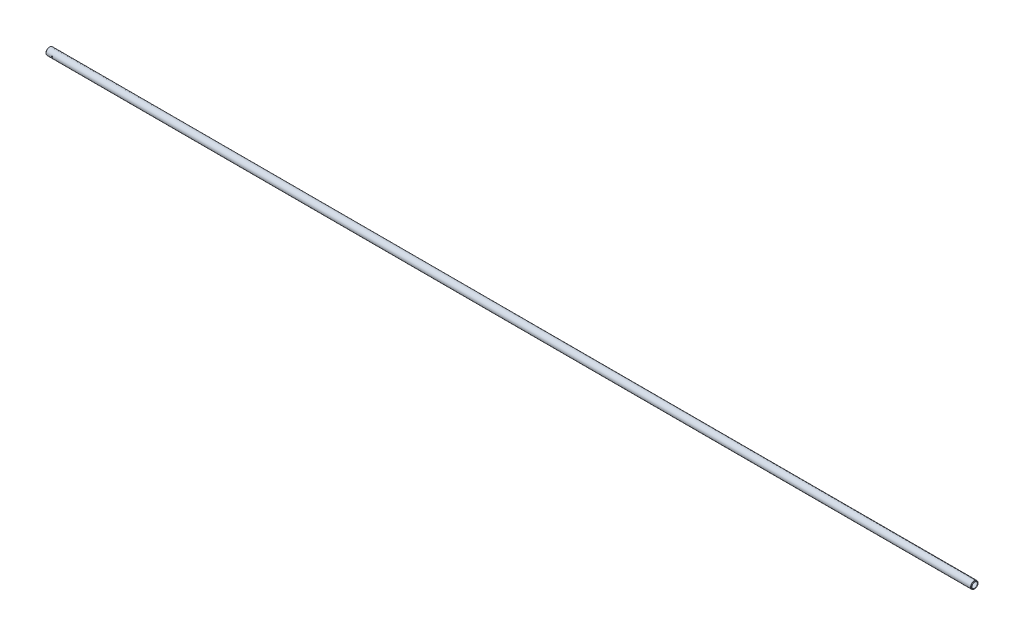
SolidWorks part; units mm, degrees
ref_plane "Front Plane" through (0, 0, 0) normal (0, 0, 1) x (1, 0, 0)
ref_plane "Top Plane" through (0, 0, 0) normal (0, 1, 0) x (1, 0, 0)
ref_plane "Right Plane" through (0, 0, 0) normal (1, 0, 0) x (0, 0, -1)
ref_plane "Plane1" through (1156.6271, 0, 0) normal (1, 0, 0) x (0, 0, -1)
sketch "Sketch1" plane through (0, 0, 0) normal (0, 0, 1) x (1, 0, 0)
  line L0 (-0.445, 3.6899) -> (-0.2794, 3.5242)
  line L1 (-0.2794, 3.5242) -> (0, 3.5242)
  line L2 (0, 3.5242) -> (0.5588, 4.0831)
  line L3 (0.5588, 4.0831) -> (1156.0683, 4.0831)
  line L4 (1156.0683, 4.0831) -> (1156.6271, 3.5242)
  line L5 (1156.6271, 3.5242) -> (1156.9065, 3.5242)
  line L6 (1156.9065, 3.5242) -> (1157.0721, 3.6899)
  line L7 (1157.0721, 3.8695) -> (1156.546, 4.3956)
  line L8 (1156.1509, 4.5593) -> (0.4762, 4.5593)
  line L9 (0.0811, 4.3956) -> (-0.445, 3.8695)
  line L10 (1156.6271, 0) -> (0, 0) construction
  arc A0 (-0.445, 3.8695) -> (-0.445, 3.6899) centre (-0.3552, 3.7797) ccw
  arc A1 (1157.0721, 3.6899) -> (1157.0721, 3.8695) centre (1156.9823, 3.7797) ccw
  arc A2 (1156.546, 4.3956) -> (1156.1509, 4.5593) centre (1156.1509, 4.0005) ccw
  arc A3 (0.4762, 4.5593) -> (0.0811, 4.3956) centre (0.4763, 4.0005) ccw
revolve "Revolve1" add sketch "Sketch1" angle 360 about L10 reverse direction yes
sketch "Sketch2" plane through (0, 0, 0) normal (0, 0, 1) x (1, 0, 0)
  circle A0 centre (7.6962, 0) radius 0.7874
extrude "Cut-Extrude1" cut sketch "Sketch2" along normal blind 4.5593
ref_plane "Plane2" through (578.3135, 0, 0) normal (1, 0, 0) x (0, 0, -1)
ref_plane "cp1 XY" through (578.3135, 0, 0) normal (1, 0, 0) x (0, 0, -1)
ref_plane "cp1 XZ" through (0, 4.5593, 0) normal (0, -1, 0) x (-1, 0, 0)
ref_plane "cp1 YZ" through (0, 0, 0) normal (0, 0, -1) x (-1, 0, 0)
ref_axis "cp1 X" through (578.3135, 4.5593, 80.9) along (0, 0, -1)
ref_axis "cp1 Y" through (578.3135, -50, 0) along (0, 1, 0)
ref_axis "cp1 Z" through (80.9, 4.5593, 0) along (-1, 0, 0)
sketch3d "cp1"
  point P0 (578.3135, 4.5593, 0)
ref_plane "cp2 XY" through (578.3135, 0, 0) normal (1, 0, 0) x (0, 0, -1)
ref_plane "cp2 XZ" through (0, 0, 0) normal (0, -1, 0) x (-1, 0, 0)
ref_plane "cp2 YZ" through (0, 0, -4.5593) normal (0, 0, -1) x (-1, 0, 0)
ref_axis "cp2 X" through (578.3135, 0, 80.9) along (0, 0, -1)
ref_axis "cp2 Y" through (578.3135, -50, -4.5593) along (0, 1, 0)
ref_axis "cp2 Z" through (80.9, 0, -4.5593) along (-1, 0, 0)
sketch3d "cp2"
  point P0 (578.3135, 0, -4.5593)
ref_plane "cp3 XY" through (578.3135, 0, 0) normal (1, 0, 0) x (0, 0, -1)
ref_plane "cp3 XZ" through (0, -4.5593, 0) normal (0, -1, 0) x (-1, 0, 0)
ref_plane "cp3 YZ" through (0, 0, 0) normal (0, 0, -1) x (-1, 0, 0)
ref_axis "cp3 X" through (578.3135, -4.5593, 80.9) along (0, 0, -1)
ref_axis "cp3 Y" through (578.3135, -50, 0) along (0, 1, 0)
ref_axis "cp3 Z" through (80.9, -4.5593, 0) along (-1, 0, 0)
sketch3d "cp3"
  point P0 (578.3135, -4.5593, 0)
ref_plane "cp4 XY" through (578.3135, 0, 0) normal (1, 0, 0) x (0, 0, -1)
ref_plane "cp4 XZ" through (0, 0, 0) normal (0, -1, 0) x (-1, 0, 0)
ref_plane "cp4 YZ" through (0, 0, 4.5593) normal (0, 0, -1) x (-1, 0, 0)
ref_axis "cp4 X" through (578.3135, 0, 80.9) along (0, 0, -1)
ref_axis "cp4 Y" through (578.3135, -50, 4.5593) along (0, 1, 0)
ref_axis "cp4 Z" through (80.9, 0, 4.5593) along (-1, 0, 0)
sketch3d "cp4"
  point P0 (578.3135, 0, 4.5593)
ref_plane "tube_front XY" through (0, 0, 0) normal (1, 0, 0) x (0, 0, -1)
ref_plane "tube_front XZ" through (0, 0, 0) normal (0, -1, 0) x (-1, 0, 0)
ref_plane "tube_front YZ" through (0, 0, 0) normal (0, 0, -1) x (-1, 0, 0)
ref_axis "tube_front X" through (0, 0, 80.9) along (0, 0, -1)
ref_axis "tube_front Y" through (0, -50, 0) along (0, 1, 0)
ref_axis "tube_front Z" through (80.9, 0, 0) along (-1, 0, 0)
sketch3d "tube_front"
  point P0 (0, 0, 0)
ref_plane "tube_rear XY" through (1156.6271, 0, 0) normal (1, 0, 0) x (0, 0, -1)
ref_plane "tube_rear XZ" through (0, 0, 0) normal (0, -1, 0) x (-1, 0, 0)
ref_plane "tube_rear YZ" through (0, 0, 0) normal (0, 0, -1) x (-1, 0, 0)
ref_axis "tube_rear X" through (1156.6271, 0, 80.9) along (0, 0, -1)
ref_axis "tube_rear Y" through (1156.6271, -50, 0) along (0, 1, 0)
ref_axis "tube_rear Z" through (80.9, 0, 0) along (-1, 0, 0)
sketch3d "tube_rear"
  point P0 (1156.6271, 0, 0)
